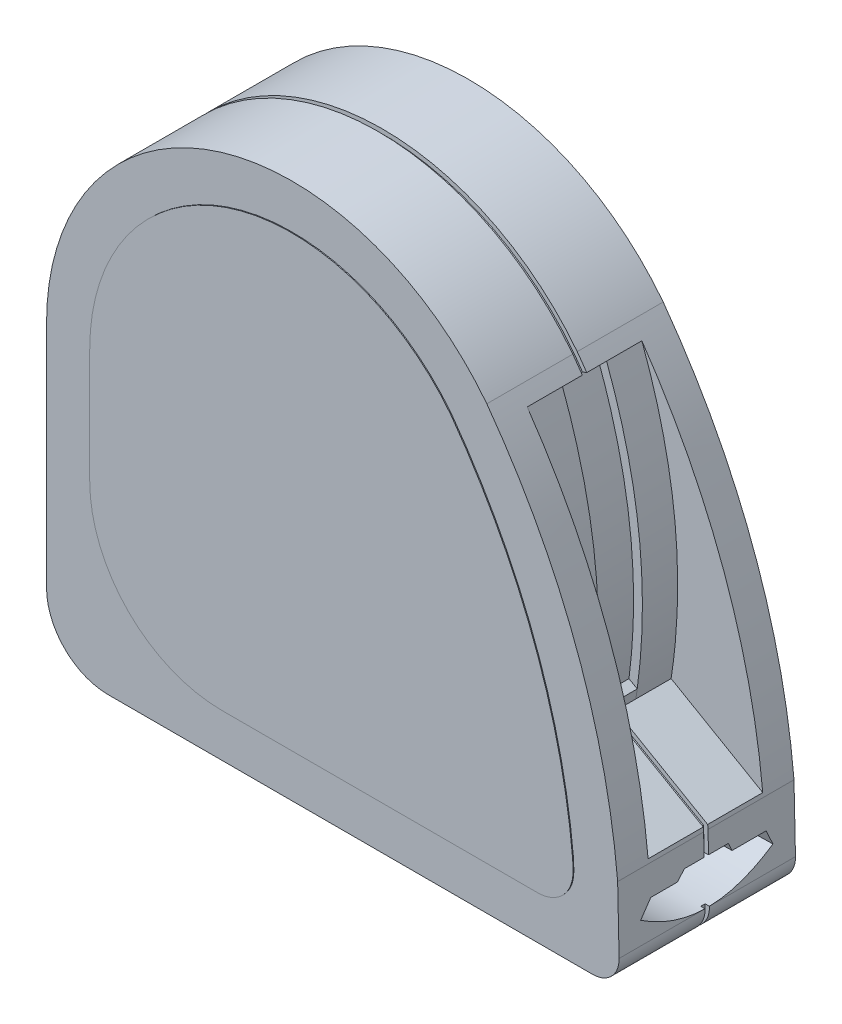
SolidWorks part; units mm, degrees
ref_plane "Front Plane" through (0, 0, 0) normal (0, 0, 1) x (1, 0, 0)
ref_plane "Top Plane" through (0, 0, 0) normal (0, 1, 0) x (1, 0, 0)
ref_plane "Right Plane" through (0, 0, 0) normal (1, 0, 0) x (0, 0, -1)
sketch "Sketch1" plane through (0, 0, 0) normal (0, 0, 1) x (1, 0, 0)
  line L0 (-3.0672, 0) -> (-58, 0)
  line L1 (-65, 7) -> (-65, 33)
  line L5 (-0.068, 3.0665) -> (-0.2335, 10.5351)
  arc A0 (-65, 33) -> (-15.068, 50.0409) centre (-37.1261, 33) cw
  arc A1 (-58, 0) -> (-65, 7) centre (-58, 7) cw
  arc A3 (-15.068, 50.0409) -> (-0.2335, 10.5351) centre (-78.9348, 3.5206) cw
  arc A4 (-3.0672, 0) -> (-0.068, 3.0665) centre (-3.0672, 3) ccw
  point P10 (-65, 0)
  point P11 (0, 0)
  dimension "D3" = 7
  dimension "D4" = 3
  dimension "D1" = 65
  dimension "D2" = 33
extrude "Boss-Extrude1" add sketch "Sketch1" along normal blind 20
ref_plane "Plane1" through (0, 0, 15) normal (0, 0, 1) x (1, 0, 0)
sketch "Sketch2" plane through (0, 0, 15) normal (0, 0, 1) x (1, 0, 0)
  line L0 (-62, 7) -> (-65, 7)
  line L1 (-58, 3) -> (-58, 0)
  arc A1 (-65, 7) -> (-58, 0) centre (-58, 7) ccw construction
  arc A2 (-62, 7) -> (-58, 3) centre (-58, 7) ccw
  arc A3 (-62, 7) -> (-58, 3) centre (-58, 7) ccw
  arc A4 (-65, 7) -> (-58, 0) centre (-58, 7) ccw
  dimension "D1" = 3
extrude "Cut-Extrude1" cut sketch "Sketch2" against normal blind 10 contours A3 L1 A4 L0
sketch "Sketch3" plane through (0, 0, 5) normal (0, 0, 1) x (1, 0, 0)
  line L0 (-62.9497, 2.0503) -> (-60.8284, 4.1716) construction
  arc A0 (-65, 7) -> (-58, 0) centre (-58, 7) ccw construction
  arc A1 (-62, 7) -> (-58, 3) centre (-58, 7) ccw construction
  circle A2 centre (-61.8891, 3.1109) radius 1
  dimension "D1" = 2
extrude "Boss-Extrude2" add sketch "Sketch3" along normal blind 11
sketch "Sketch4" plane through (0, 0, 0) normal (0.9998, 0.0222, 0) x (0, 0, -1)
  line L0 (-16.3164, 7.1734) -> (-13.2773, 7.1734)
  line L1 (-13.2773, 7.1734) -> (-12.5, 8.0672)
  line L2 (-12.5, 8.0672) -> (-7.5, 8.0672)
  line L3 (-7.5, 8.0672) -> (-7.0978, 7.1734)
  line L4 (-7.0978, 7.1734) -> (-3.2375, 7.1734)
  line L5 (-3.2375, 7.1734) -> (-2.5, 5.5344)
  line L6 (-17.5, 5.5344) -> (-16.3164, 7.1734)
  line L7 (-20, 3.0672) -> (0, 3.0672) construction
  line L8 (-10, 10.5377) -> (-10, 3.0672) construction
  line L9 (-20, 10.5377) -> (0, 10.5377) construction
  line L10 (-10.2319, 2.0672) -> (-9.577, 2.0672) construction
  spline S0 degree 2 poles (-2.5, 5.5344) (-10, 0.6001) (-17.5, 5.5344) knots 0 0 0 1 1 1
  dimension "D1" = 5
  dimension "D2" = 5
  dimension "D3" = 2.5
  dimension "D4" = 6
  dimension "D5" = 15
  dimension "D6" = 7.5
extrude "Cut-Extrude2" cut sketch "Sketch4" against normal blind 48
ref_plane "Plane2" through (0, 0, 16.5) normal (0, 0, 1) x (1, 0, 0)
sketch "Sketch5" plane through (0, 0, 16.5) normal (0, 0, 1) x (1, 0, 0)
  line L0 (-0.2763, 11) -> (-10.6686, 17)
  line L2 (-58, 0) -> (-3.0672, 0) construction
  line L3 (-0.2763, 11) -> (-8.7239, 11) construction
  arc A0 (-0.2335, 10.5351) -> (-15.068, 50.0409) centre (-78.9348, 3.5206) ccw construction
  arc A2 (-15.068, 50.0409) -> (-65, 33) centre (-37.1261, 33) ccw construction
  arc A4 (-0.2763, 11) -> (-13.9876, 48.5202) centre (-78.9348, 3.5206) ccw
  spline S0 degree 2 poles (-10.6686, 17) (-8.1813, 33.0226) (-14.0062, 48.5698) knots 0 0 0 1 1 1
  dimension "D1" = 11
  dimension "D2" = 12
  dimension "D3" = 30
  dimension "D4" = 40
extrude "Cut-Extrude3" cut sketch "Sketch5" against normal blind 4 contours S0 L0 A4 region at (-6.7058, 25.4851, 16.5)
sketch "Sketch7" plane through (0, 0, 12.5) normal (0, 0, 1) x (1, 0, 0)
  line L0 (-13.9876, 48.5202) -> (-14.9243, 48.1701)
  line L2 (-0.9027, 11.3617) -> (-0.2763, 11)
  line L7 (-0.9027, 11.3617) -> (-10.6686, 17)
  line L8 (-10.5125, 18.0645) -> (-11.4486, 18.605)
  arc A2 (-0.2335, 10.5351) -> (-15.068, 50.0409) centre (-78.9348, 3.5206) ccw construction
  arc A3 (-0.2763, 11) -> (-13.9876, 48.5202) centre (-78.9348, 3.5206) ccw
  parabola Q1 (-10.6686, 17) -> (-13.9876, 48.5202) focus (-40.1645, 28.2757) apex (-10.0229, 29.9992) construction
  parabola Q2 (-10.6686, 17) -> (-10.5125, 18.0645) focus (-40.1645, 28.2757) apex (-10.0229, 29.9992)
  spline S0 degree 3 poles (-2787.3018, -1109.9128) (-889.7505, -397.89) (8.7628, -157.2986) (-30.8553, 218.9533) (-931.9484, 357.3449) (-2923.6713, 760.0271) knots -17.894128 -17.894128 -17.894128 -17.894128 0.5 0.5 18.517398 18.517398 18.517398 18.517398 only from (-11.6568, 17.1534) to (-14.9243, 48.1701)
  spline S1 degree 3 poles (-11.4486, 18.605) (-10.8227, 23.3629) (-10.7573, 28.0838) (-11.7952, 37.9405) (-13.0181, 43.0703) (-14.9243, 48.1701) knots 0.046122 0.046122 0.046122 0.046122 0.5 0.5 1 1 1 1
  point P3 (0.2237, 11.866)
  point P8 (-10.1686, 17.866)
  dimension "D1" = 1
extrude "Cut-Extrude4" cut sketch "Sketch7" against normal blind 5
sketch "Sketch8" plane through (0, 0, 7.5) normal (0, 0, 1) x (1, 0, 0)
  line L0 (-0.2763, 11) -> (-10.6686, 17) construction
  line L1 (-0.2763, 11) -> (-10.6686, 17)
  arc A0 (-0.2763, 11) -> (-13.9876, 48.5202) centre (-78.9348, 3.5206) ccw construction
  arc A1 (-0.2763, 11) -> (-13.9876, 48.5202) centre (-78.9348, 3.5206) ccw
  parabola Q0 (-10.6686, 17) -> (-13.9876, 48.5202) focus (-40.1645, 28.2757) apex (-10.0229, 29.9992) construction
  parabola Q1 (-10.6686, 17) -> (-13.9876, 48.5202) focus (-40.1645, 28.2757) apex (-10.0229, 29.9992)
extrude "Cut-Extrude5" cut sketch "Sketch8" against normal blind 4
ref_plane "Plane3" through (0, 0, 10.25) normal (0, 0, 1) x (1, 0, 0)
sketch "Sketch9" plane through (0, 0, 10.25) normal (0, 0, 1) x (1, 0, 0)
  line L13 (-65, 33) -> (-65, 7)
  line L14 (-58, 0) -> (-3.0672, 0)
  line L15 (-0.068, 3.0665) -> (-0.2335, 10.5351)
  line L16 (-0.5678, 3.0554) -> (-0.733, 10.5073)
  line L17 (-58, 0.5) -> (-3.0672, 0.5)
  line L18 (-64.5, 33) -> (-64.5, 7)
  line L19 (-0.5678, 3.0554) -> (-0.733, 10.5073)
  line L20 (-58, 0.5) -> (-3.0672, 0.5)
  line L21 (-64.5, 33) -> (-64.5, 7)
  arc A16 (-15.068, 50.0409) -> (-65, 33) centre (-37.1261, 33) ccw
  arc A17 (-65, 7) -> (-58, 0) centre (-58, 7) ccw
  arc A18 (-3.0672, 0) -> (-0.068, 3.0665) centre (-3.0672, 3) ccw
  arc A19 (-0.2335, 10.5351) -> (-15.068, 50.0409) centre (-78.9348, 3.5206) ccw
  arc A20 (-0.733, 10.5073) -> (-15.468, 49.7408) centre (-78.9348, 3.5206) ccw
  arc A21 (-3.0672, 0.5) -> (-0.5678, 3.0554) centre (-3.0672, 3) ccw
  arc A22 (-64.5, 7) -> (-58, 0.5) centre (-58, 7) ccw
  arc A23 (-15.468, 49.7408) -> (-64.5, 33) centre (-37.1261, 33) ccw
  arc A24 (-0.733, 10.5073) -> (-15.468, 49.7408) centre (-78.9348, 3.5206) ccw
  arc A25 (-3.0672, 0.5) -> (-0.5678, 3.0554) centre (-3.0672, 3) ccw
  arc A26 (-64.5, 7) -> (-58, 0.5) centre (-58, 7) ccw
  arc A27 (-15.468, 49.7408) -> (-64.5, 33) centre (-37.1261, 33) ccw
  dimension "D1" = 0.5
  dimension "D2" = 0.5
extrude "Cut-Extrude6" cut sketch "Sketch9" against normal blind 0.5
sketch "Sketch10" plane through (4.6941, 8.1304, 0) normal (0.5, 0.866, 0) x (0.866, -0.5, 0)
  line L0 (-33.4806, -10.25) -> (33.4806, -10.25) construction
  line L1 (-5.8574, -9.75) -> (-17.7393, -9.75)
  line L2 (-5.8574, -9.75) -> (-5.8574, -10.25)
  line L3 (-5.8574, -10.25) -> (-17.7393, -10.25)
  line L4 (-17.7393, -9.75) -> (-17.7393, -10.25)
  line L5 (-17.7393, -7.5) -> (-17.7393, -12.5) construction
extrude "Cut-Extrude8" cut sketch "Sketch10" against normal blind 0.5
sketch "Sketch12" plane through (0, 0, 20) normal (0, 0, 1) x (1, 0, 0)
  line L13 (-60, 33) -> (-60, 20)
  line L14 (-9.2017, 5) -> (-45, 5)
  line L16 (-5.112, 5) -> (-5.2285, 10.2547)
  line L17 (-58, 5) -> (-5.112, 5)
  line L18 (-60, 33) -> (-60, 7)
  line L19 (-5.2027, 9.0886) -> (-5.2285, 10.2547)
  arc A15 (-45, 5) -> (-60, 20) centre (-45, 20) cw
  arc A16 (-5.2027, 9.0886) -> (-9.2017, 5) centre (-9.2017, 9) cw
  arc A19 (-5.2285, 10.2547) -> (-19.0666, 47.0381) centre (-78.9348, 3.5206) ccw
  arc A20 (-60, 7) -> (-58, 5) centre (-58, 7) ccw
  arc A21 (-19.0666, 47.0381) -> (-60, 33) centre (-37.1261, 33) ccw
  arc A22 (-5.2285, 10.2547) -> (-19.0666, 47.0381) centre (-78.9348, 3.5206) ccw
  arc A24 (-19.0666, 47.0381) -> (-60, 33) centre (-37.1261, 33) ccw
  dimension "D2" = 15
  dimension "D3" = 4
  dimension "D1" = 5
sketch "Sketch13" plane through (0, 0, 0) normal (0, 0, -1) x (-1, 0, 0)
  line L0 (0.2216, 10) -> (65, 10) construction
  line L1 (0.068, 3.0665) -> (0.2335, 10.5351) construction
  line L2 (65, 33) -> (65, 7) construction
  line L3 (58, 0) -> (3.0672, 0) construction
  circle A0 centre (9.2238, 10) radius 2.5
  circle A1 centre (59.2238, 10) radius 2.5
  dimension "D2" = 5
  dimension "D5" = 5
  dimension "D1" = 10
  dimension "D3" = 9
  dimension "D4" = 50
extrude "Boss-Extrude4" add sketch "Sketch13" along normal blind 0.5
sketch "Sketch14" plane through (0, 0, -0.5) normal (0, 0, -1) x (-1, 0, 0)
  line L0 (9.2238, 12.5) -> (9.2238, 7.5) construction
  line L1 (8.9738, 11.75) -> (9.4738, 11.75)
  line L2 (8.9738, 11.75) -> (8.9738, 10.25)
  line L3 (8.9738, 8.25) -> (9.4738, 8.25)
  line L4 (9.4738, 11.75) -> (9.4738, 10.25)
  line L5 (7.4738, 10.25) -> (8.9738, 10.25)
  line L6 (7.4738, 10.25) -> (7.4738, 9.75)
  line L7 (7.4738, 9.75) -> (8.9738, 9.75)
  line L8 (10.9738, 10.25) -> (10.9738, 9.75)
  line L9 (6.7238, 10) -> (11.7238, 10) construction
  line L10 (34.2238, 0) -> (34.2238, 28.0922) construction
  line L11 (58, 0) -> (3.0672, 0) construction
  line L12 (60.9738, 9.75) -> (59.4738, 9.75)
  line L13 (57.4738, 10.25) -> (57.4738, 9.75)
  line L14 (60.9738, 10.25) -> (59.4738, 10.25)
  line L15 (60.9738, 10.25) -> (60.9738, 9.75)
  line L16 (59.4738, 8.25) -> (58.9738, 8.25)
  line L17 (58.9738, 11.75) -> (58.9738, 10.25)
  line L18 (59.4738, 11.75) -> (58.9738, 11.75)
  line L19 (59.4738, 11.75) -> (59.4738, 10.25)
  line L20 (9.4738, 9.75) -> (9.4738, 8.25)
  line L21 (9.4738, 10.25) -> (10.9738, 10.25)
  line L22 (8.9738, 9.75) -> (8.9738, 8.25)
  line L23 (9.4738, 9.75) -> (10.9738, 9.75)
  line L24 (59.4738, 9.75) -> (59.4738, 8.25)
  line L25 (58.9738, 10.25) -> (57.4738, 10.25)
  line L26 (58.9738, 9.75) -> (58.9738, 8.25)
  line L27 (58.9738, 9.75) -> (57.4738, 9.75)
  circle A0 centre (9.2238, 10) radius 2.5 construction
  circle A1 centre (9.2238, 10) radius 2.5 construction
  dimension "D1" = 0.5
  dimension "D2" = 0.5
  dimension "D3" = 3.5
  dimension "D4" = 3.5
  dimension "D5" = 1.5
  dimension "D6" = 1.5
  dimension "D7" = 0.25
  dimension "D8" = 0.25
  dimension "D9" = 25
extrude "Cut-Extrude11" cut sketch "Sketch14" against normal blind 0.5
fillet "Fillet1" radius 4.5 2 edges at (-61.7238, 10, -0.5) (-11.7238, 10, -0.5)
sketch "Sketch18" plane through (0, 0, 0) normal (0, 0, -1) x (-1, 0, 0)
  line L0 (58, 0) -> (3.0672, 0) construction
  line L2 (26, 45.13) -> (26, 22)
  line L3 (26, 22) -> (47, 22)
  line L4 (47, 45.13) -> (47, 22)
  line L5 (65, 33) -> (65, 7) construction
  line L6 (25.5, 45.13) -> (25.5, 21.5)
  line L7 (25.5, 21.5) -> (47.5, 21.5)
  line L8 (47.5, 45.13) -> (47.5, 21.5)
  line L10 (26, 45.13) -> (25.5, 45.13)
  line L11 (47, 45.13) -> (47.5, 45.13)
  line L13 (47.5, 45.63) -> (47.5, 21.5) construction
  line L14 (25.5, 45.63) -> (47.5, 45.63) construction
  line L15 (26, 45.13) -> (47, 45.13) construction
  line L16 (25.5, 45.63) -> (25.5, 21.5) construction
  dimension "D1" = 21
  dimension "D2" = 23.13
  dimension "D3" = 22
  dimension "D4" = 18
  dimension "D5" = 0.5
extrude "Boss-Extrude6" add sketch "Sketch18" along normal blind 0.25
extrude "Boss-Extrude7" add sketch "Sketch12" along normal blind 0.1
